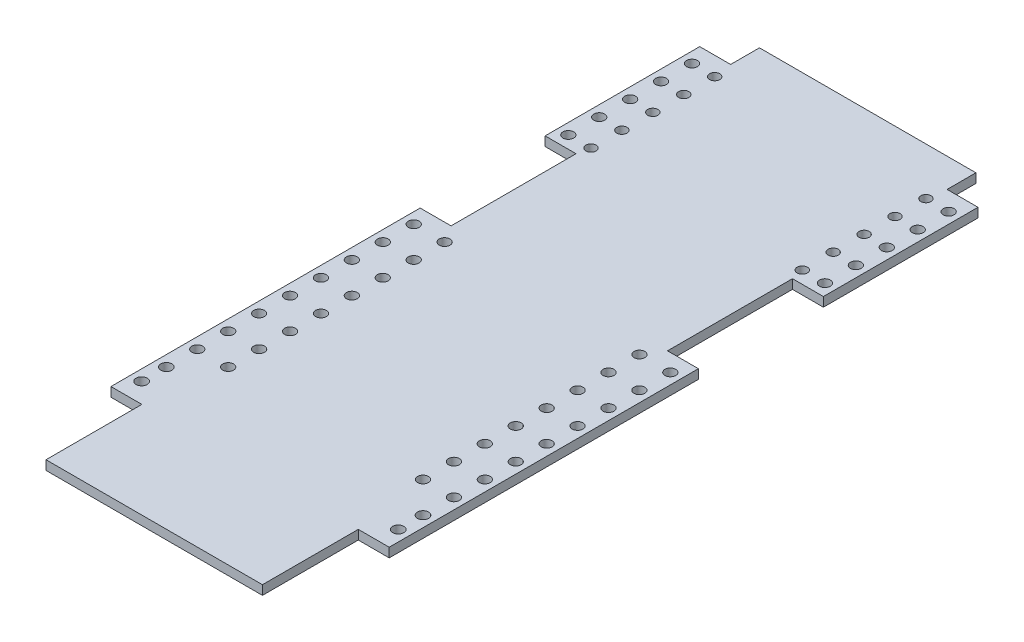
SolidWorks part; units mm, degrees
ref_plane "Front Plane" through (0, 0, 0) normal (0, 0, 1) x (1, 0, 0)
ref_plane "Top Plane" through (0, 0, 0) normal (0, 1, 0) x (1, 0, 0)
ref_plane "Right Plane" through (0, 0, 0) normal (1, 0, 0) x (0, 0, -1)
sketch "Sketch5" plane through (0, 0, 0) normal (0, 1, 0) x (1, 0, 0)
  line L0 (70, 36) -> (80, 36)
  line L1 (0, 0) -> (70, 0)
  line L2 (0, 0) -> (0, 235.74)
  line L3 (0, 235.74) -> (70, 235.74)
  line L4 (70, 0) -> (70, 235.74)
  line L5 (80, 36) -> (80, 136)
  line L6 (80, 136) -> (70, 136)
  line L7 (35, 235.74) -> (35, 0) construction
  line L8 (-10, 136) -> (0, 136)
  line L9 (-10, 36) -> (-10, 136)
  line L10 (0, 36) -> (-10, 36)
  dimension "D1" = 235.74
  dimension "D2" = 70
  dimension "D3" = 36
  dimension "D4" = 100
  dimension "D5" = 10
extrude "Boss-Extrude5" add sketch "Sketch5" along normal blind 3 contours L10 L2 L8 L9 | L7 L3 L2 L1 | L3 L7 L1 L4 | L5 L6 L4 L0 region at (75, 0, -86) region at (52.5, 0, -117.87) region at (17.5, 0, -117.87) region at (-5, 0, -86)
sketch "Sketch6" plane through (0, 3, 0) normal (0, 1, 0) x (1, 0, 0)
  point P0 (76.5, 50.42)
  point P3 (76.5, 42.42)
hole_wizard "M3 Clearance Hole1" positions "Sketch6" profile "Sketch7" hole size "M3" standard "ANSI Metric" end condition through all
sketch "Sketch7" plane through (76.5, 3, -50.42) normal (1, 0, 0) x (0, 0, 1)
  line L0 (0, 0) -> (0, 3)
  line L1 (0, 3) -> (1.8, 3)
  line L2 (1.8, 3) -> (1.8, 0)
  line L5 (1.8, 0) -> (0, 0)
  line L11 (0, -6.35) -> (0, 107.95) construction
  dimension "Thru Hole Dia." = 3.6
  dimension "Thru Hole Depth" = 3
ref_plane "Plane1" through (35, 0, 0) normal (-1, 0, 0) x (0, 0, 1)
sketch "Sketch8" plane through (0, 3, 0) normal (0, 1, 0) x (1, 0, 0)
  line L0 (80, 36) -> (80, 136) construction
  circle A0 centre (76.5, 60.42) radius 1.75
  circle A4 centre (76.5, 50.42) radius 1.8 construction
  circle A6 centre (66.5, 60.42) radius 1.75
  circle A7 centre (66.5, 70.42) radius 1.75
  circle A8 centre (66.5, 80.42) radius 1.75
  circle A9 centre (66.5, 90.42) radius 1.75
  circle A10 centre (66.5, 100.42) radius 1.75
  circle A11 centre (66.5, 110.42) radius 1.75
  circle A12 centre (66.5, 120.42) radius 1.75
  circle A13 centre (66.5, 130.42) radius 1.75
  circle A14 centre (76.5, 70.42) radius 1.75
  circle A15 centre (76.5, 80.42) radius 1.75
  circle A16 centre (76.5, 90.42) radius 1.75
  circle A17 centre (76.5, 100.42) radius 1.75
  circle A18 centre (76.5, 110.42) radius 1.75
  circle A19 centre (76.5, 120.42) radius 1.75
  circle A20 centre (76.5, 130.42) radius 1.75
  dimension "D1" = 3.5
  dimension "D3" = 10
  dimension "D2" = 3.5
  dimension "D4" = 2
  dimension "D5" = 8
extrude "Cut-Extrude1" cut sketch "Sketch8" against normal through all
sketch "Sketch10" plane through (0, 0, 0) normal (0, -1, 0) x (1, 0, 0)
  line L0 (70, -176.42) -> (80, -176.42)
  line L1 (70, -136) -> (70, -235.74) construction
  line L2 (80, -176.42) -> (80, -226.42)
  line L3 (80, -226.42) -> (70, -226.42)
  line L4 (70, -226.42) -> (70, -176.42)
  circle A0 centre (76.5, -180.42) radius 1.75
  circle A4 centre (76.5, -130.42) radius 1.75 construction
  circle A5 centre (76.5, -190.42) radius 1.75
  circle A8 centre (76.5, -200.42) radius 1.75
  circle A9 centre (76.5, -210.42) radius 1.75
  circle A10 centre (76.5, -220.42) radius 1.75
  dimension "D8" = 3.5
  dimension "D11" = 3.5
  dimension "D3" = 50
  dimension "D1" = 10
  dimension "D2" = 50
  dimension "D4" = 5
  dimension "D7" = 4
extrude "Boss-Extrude6" add sketch "Sketch10" against normal blind 3
sketch "Sketch11" plane through (0, 3, 0) normal (0, 1, 0) x (1, 0, 0)
  circle A13 centre (76.5, 180.42) radius 1.75 construction
  circle A14 centre (76.5, 180.42) radius 1.75 construction
  circle A15 centre (69.1652, 180.4206) radius 1.65
  circle A16 centre (69.1652, 190.4206) radius 1.65
  circle A17 centre (69.1652, 200.4206) radius 1.65
  circle A18 centre (69.1652, 210.4206) radius 1.65
  circle A19 centre (69.1652, 220.4206) radius 1.65
  dimension "D1" = 3.3
  dimension "D2" = 5
extrude "Cut-Extrude2" cut sketch "Sketch11" against normal through all
mirror "Mirror1" about plane through (35, 0, 0) normal (-1, 0, 0) of "Cut-Extrude2", "Boss-Extrude6", "M3 Clearance Hole1", "Cut-Extrude1"
sketch "Sketch12" plane through (0, 3, 0) normal (0, 1, 0) x (1, 0, 0)
  line L0 (70, 0) -> (70, 36) construction
  line L1 (0, 0) -> (70, 0)
  line L2 (0, 0) -> (0, 5)
  line L3 (0, 5) -> (70, 5)
  line L4 (70, 0) -> (70, 5)
  dimension "D1" = 5
extrude "Cut-Extrude3" cut sketch "Sketch12" against normal blind 10
equation "\"Spacing\"=8"
